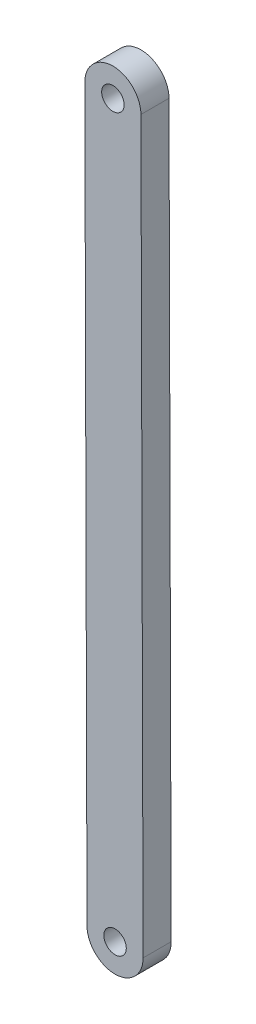
SolidWorks part; units mm, degrees
ref_plane "Front Plane" through (0, 0, 0) normal (0, 0, 1) x (1, 0, 0)
ref_plane "Top Plane" through (0, 0, 0) normal (0, 1, 0) x (1, 0, 0)
ref_plane "Right Plane" through (0, 0, 0) normal (1, 0, 0) x (0, 0, -1)
sketch "Sketch1" plane through (0, 0, 0) normal (0, 0, 1) x (1, 0, 0)
  line L0 (-6.1835, 155.9532) -> (-5.7958, 25.9538)
  line L1 (-15.7957, 25.924) -> (-16.1835, 155.9234)
  circle A0 centre (-10.7957, 25.9389) radius 2 construction
  circle A1 centre (-10.7957, 25.9389) radius 2
  circle A2 centre (-11.1835, 155.9383) radius 2 construction
  circle A3 centre (-11.1835, 155.9383) radius 2
  arc A4 (-5.7958, 25.9538) -> (-15.7957, 25.924) centre (-10.7957, 25.9389) cw
  arc A5 (-16.1835, 155.9234) -> (-6.1835, 155.9532) centre (-11.1835, 155.9383) cw
  dimension "D1" = 5
  dimension "D2" = 5
extrude "Boss-Extrude1" add sketch "Sketch1" along normal blind 5 from offset 5
